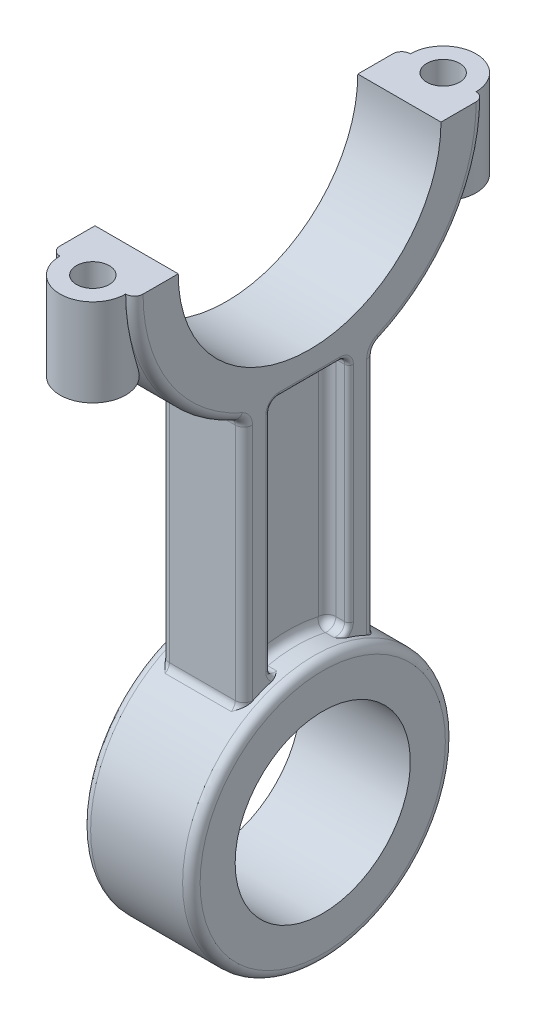
SolidWorks part; units mm, degrees
ref_plane "Front Plane" through (0, 0, 0) normal (1, 0, 0) x (0, 1, 0)
ref_plane "Top Plane" through (0, 0, 0) normal (0, 0, 1) x (0, 1, 0)
ref_plane "Right Plane" through (0, 0, 0) normal (0, 1, 0) x (-1, 0, 0)
sketch "Sketch1" plane through (0, 0, 0) normal (1, 0, 0) x (0, 1, 0)
  line L0 (-76.2, 0) -> (76.2, 0) construction
  line L1 (-59.3995, 19.05) -> (29.1071, 19.05)
  line L2 (-59.3995, 19.05) -> (-59.3995, -19.05) construction
  line L3 (-59.3995, -19.05) -> (29.1071, -19.05)
  line L5 (-59.3995, 19.05) -> (59.3995, -19.05) construction
  line L6 (-59.3995, -19.05) -> (59.3995, 19.05) construction
  line L7 (76.2, 50.8) -> (76.2, 38.1)
  line L8 (76.2, -38.1) -> (76.2, -50.8)
  circle A0 centre (-76.2, 0) radius 25.4
  circle A1 centre (-76.2, 0) radius 38.1
  arc A2 (76.2, 38.1) -> (76.2, -38.1) centre (76.2, 0) ccw
  arc A3 (76.2, 50.8) -> (76.2, -50.8) centre (76.2, 0) ccw
  circle A4 centre (76.2, 0) radius 50.8 construction
  circle A5 centre (76.2, 0) radius 38.1 construction
  point P0 (0, 0)
  dimension "D3" = 50.8
  dimension "D5" = 76.2
  dimension "D1" = 152.4
  dimension "D2" = 38.1
  dimension "D4" = 12.7
  dimension "D6" = 12.7
extrude "Boss-Extrude1" add sketch "Sketch1" along normal mid plane 24.13 contours L3 A1 L1 A0 | A3 L1 A1 L3 | L7 A3 L8 A2 | L1 A1 L3 A0 region at (0, -102.6422, 0) region at (0, -46.7377, 0) region at (0, -6.576, 0) region at (0, 48.4369, 41.1793)
extrude "Boss-Extrude2" add sketch "Sketch1<3>" along normal mid plane 31.75 contours A1 | A0
sketch "Sketch1<3>" plane through (0, 0, 0) normal (1, 0, 0) x (0, 1, 0) same geometry as "Sketch1"
sketch "Sketch3" plane through (0, 76.2, 0) normal (0, 1, 0) x (-1, 0, 0)
  line L0 (-12.065, -50.8) -> (12.065, -50.8) construction
  circle A0 centre (0, -50.8) radius 9.525
  dimension "D1" = 19.05
extrude "Boss-Extrude3" add sketch "Sketch3" against normal blind 25.4
sketch "Sketch4" plane through (0, 76.2, 0) normal (0, 1, 0) x (-1, 0, 0)
  circle A0 centre (0, -50.8) radius 4.76
  arc A1 (-9.525, -50.8) -> (9.525, -50.8) centre (0, -50.8) ccw construction
  dimension "D1" = 9.52
extrude "Cut-Extrude1" cut sketch "Sketch4" against normal blind 25.4
mirror "Mirror3" about plane through (0, 0, 0) normal (0, 0, 1) of "Cut-Extrude1", "Boss-Extrude3"
sketch "Sketch7" plane through (12.065, 0, 0) normal (1, 0, 0) x (0, 1, 0)
  line L0 (-43.2044, 19.05) -> (29.1071, 19.05) construction
  line L1 (30.5854, -11.43) -> (-39.8549, -11.43)
  line L2 (30.5854, -11.43) -> (30.5854, 11.43)
  line L3 (30.5854, 11.43) -> (-39.8549, 11.43)
  line L4 (-39.8549, -11.43) -> (-39.8549, 11.43) construction
  line L5 (30.5854, -11.43) -> (-39.8549, 11.43) construction
  line L6 (30.5854, 11.43) -> (-39.8549, -11.43) construction
  arc A0 (-43.2044, -19.05) -> (-43.2044, 19.05) centre (-76.2, 0) ccw construction
  circle A1 centre (-76.2, 0) radius 38.1 construction
  arc A2 (-39.8549, -11.43) -> (-39.8549, 11.43) centre (-76.2, 0) ccw
  point P0 (-4.6348, 0)
  dimension "D1" = 7.62
extrude "Cut-Extrude2" cut sketch "Sketch7" against normal blind 6.35
mirror "Mirror4" about plane through (0, 0, 0) normal (1, 0, 0) of "Cut-Extrude2"
fillet "Fillet2" radius 2.54 22 edges at (-15.875, -76.2, -38.1) (15.875, -76.2, -38.1) (-5.715, -4.6348, -11.43) (-5.715, 30.5854, 0) (-5.715, -4.6348, 11.43) (-5.715, -38.1, 0) (5.715, -4.6348, 11.43) (5.715, 30.5854, 0) (5.715, -4.6348, -11.43) (5.715, -38.1, 0) (0, 29.1071, -19.05) (0, -43.2044, -19.05) (0, 29.1071, 19.05) (0, -43.2044, 19.05) (8.89, 30.5854, -11.43) (8.89, 30.5854, 11.43) (8.89, -39.8549, 11.43) (8.89, -39.8549, -11.43) (-8.89, 30.5854, -11.43) (-8.89, 30.5854, 11.43) (-8.89, -39.8549, 11.43) (-8.89, -39.8549, -11.43)
fillet "Fillet3" radius 1.27 14 edges at (-12.065, -38.527, -10.4775) (-12.065, -38.527, 10.4775) (-12.065, -4.2495, 11.43) (-12.065, 29.8414, 10.6861) (-12.065, 30.5854, 0) (-12.065, 29.8414, -10.6861) (12.065, -38.527, -10.4775) (12.065, -38.527, 10.4775) (12.065, -4.2495, 11.43) (12.065, 29.8414, 10.6861) (12.065, 30.5854, 0) (12.065, 29.8414, -10.6861) (-12.065, -4.2495, -11.43) (12.065, -4.2495, -11.43)
fillet "Fillet5" radius 2.5 16 edges at (-12.065, -42.9989, 19.3675) (-12.065, 48.4863, 42.5746) (-12.065, 28.8104, 19.4613) (12.065, -42.9989, 19.3675) (12.065, 48.4863, 42.5746) (12.065, 28.8104, 19.4613) (-12.065, -42.9989, -19.3675) (-12.065, 48.4863, -42.5746) (-12.065, 28.8104, -19.4613) (12.065, -42.9989, -19.3675) (12.065, 48.4863, -42.5746) (12.065, 28.8104, -19.4613) (-12.065, -7.1722, 19.05) (12.065, -7.1722, 19.05) (-12.065, -7.1722, -19.05) (12.065, -7.1722, -19.05)
